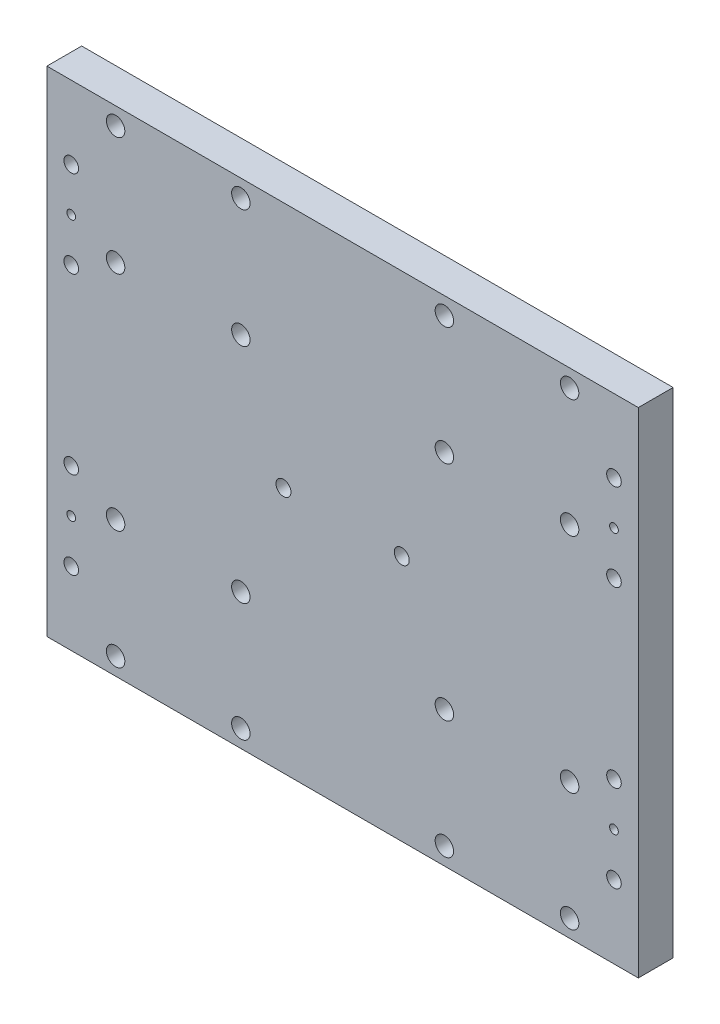
SolidWorks part; units mm, degrees
ref_plane "Front Plane" through (0, 0, 0) normal (0, 0, 1) x (1, 0, 0)
ref_plane "Top Plane" through (0, 0, 0) normal (0, 1, 0) x (1, 0, 0)
ref_plane "Right Plane" through (0, 0, 0) normal (1, 0, 0) x (0, 0, -1)
sketch "Sketch1" plane through (0, 0, 0) normal (0, 0, 1) x (1, 0, 0)
  line L1 (85, -71) -> (-85, -71)
  line L2 (85, -71) -> (85, 71)
  line L3 (85, 71) -> (-85, 71)
  line L4 (-85, -71) -> (-85, 71)
  line L5 (85, -71) -> (-85, 71) construction
  line L6 (85, 71) -> (-85, -71) construction
  point P0 (0, 0)
  dimension "D1" = 170
  dimension "D2" = 142
extrude "Boss-Extrude1" add sketch "Sketch1" along normal mid plane 10
hole_wizard "M5 Clearance Hole1" positions "Sketch8" profile "Sketch7" hole size "M5" standard "ANSI Metric" end condition through all
sketch "Sketch8" plane through (0, 0, 5) normal (0, 0, 1) x (1, 0, 0)
  line L1 (-29.25, 32) -> (-65.25, 32) construction
  line L2 (-29.25, 32) -> (-29.25, 66) construction
  line L3 (-29.25, 66) -> (-65.25, 66) construction
  line L4 (-65.25, 32) -> (-65.25, 66) construction
  line L5 (-29.25, 32) -> (-65.25, 66) construction
  line L6 (-29.25, 66) -> (-65.25, 32) construction
  line L9 (85, 71) -> (-85, 71) construction
  line L10 (-85, 71) -> (-85, -71) construction
  point P0 (-65.25, 66)
  point P2 (-29.25, 66)
  point P4 (-29.25, 32)
  point P6 (-65.25, 32)
  dimension "D1" = 5
  dimension "D2" = 19.75
  dimension "D3" = 34
  dimension "D4" = 36
sketch "Sketch7" plane through (-65.25, 66, 5) normal (1, 0, 0) x (0, -1, 0)
  line L0 (0, 0) -> (0, 10)
  line L1 (0, 10) -> (2.65, 10)
  line L2 (2.65, 10) -> (2.65, 0)
  line L5 (2.65, 0) -> (0, 0)
  line L11 (0, -6.35) -> (0, 107.95) construction
  dimension "Thru Hole Dia." = 5.3
  dimension "Thru Hole Depth" = 10
mirror "Mirror2" about plane through (0, 0, 0) normal (0, 1, 0) of "M5 Clearance Hole1"
mirror "Mirror3" about plane through (0, 0, 0) normal (1, 0, 0) of "Mirror2"
hole_wizard "M4 Clearance Hole1" positions "Sketch10" profile "Sketch9" hole size "M4" standard "ANSI Metric" end condition through all
sketch "Sketch10" plane through (0, 0, 5) normal (0, 0, 1) x (1, 0, 0)
  line L0 (-1000, 0) -> (49000, 0) construction
  point P0 (-17, 0)
  point P2 (17, 0)
  dimension "D1" = 17
  dimension "D2" = 17
sketch "Sketch9" plane through (-17, 0, 5) normal (1, 0, 0) x (0, -1, 0)
  line L0 (0, 0) -> (0, 10)
  line L1 (0, 10) -> (2.15, 10)
  line L2 (2.15, 10) -> (2.15, 0)
  line L5 (2.15, 0) -> (0, 0)
  line L11 (0, -6.35) -> (0, 107.95) construction
  dimension "Thru Hole Dia." = 4.3
  dimension "Thru Hole Depth" = 10
hole_wizard "M5x0.8 Tapped Hole1" positions "Sketch12" profile "Sketch11" tap size "M5x0.8" standard "ANSI Metric"
sketch "Sketch12" plane through (0, 0, 5) normal (0, 0, 1) x (1, 0, 0)
  line L0 (-78, -1023.3996) -> (-78, 48976.6004) construction
  line L1 (-85, 71) -> (-85, -71) construction
  line L2 (-1000, 0) -> (49000, 0) construction
  point P0 (-78, 50)
  point P2 (-78, 25)
  dimension "D1" = 7
  dimension "D2" = 25
  dimension "D3" = 50
sketch "Sketch11" plane through (-78, 50, 5) normal (1, 0, 0) x (0, -1, 0)
  line L0 (0, 0) -> (0, 15.2618)
  line L1 (0, 15.2618) -> (2.1, 14)
  line L2 (2.1, 14) -> (2.1, 0)
  line L5 (2.1, 0) -> (0, 0)
  line L10 (0, 15.2618) -> (-2.1, 14) construction
  line L11 (0, -6.35) -> (0, 107.95) construction
  dimension "Tap Drill Dia." = 4.2
  dimension "Tap Drill Depth" = 14
  dimension "Drill Angle" = 118
cosmetic thread "Hole Thread1" parameters "D1"=10, "D2"=5
cosmetic thread "Hole Thread2" parameters "D1"=10, "D2"=5
sketch "Sketch6" plane through (0, 0, 5) normal (0, 0, 1) x (1, 0, 0)
  line L0 (-78, -1002.1032) -> (-78, 48997.8968) construction
  line L1 (78, -1010.3548) -> (78, 48989.6452) construction
  line L2 (-85, 71) -> (-85, -71) construction
  line L3 (85, -71) -> (85, 71) construction
  line L6 (-1000, 0) -> (49000, 0) construction
  circle A1 centre (-78, 37.5) radius 1.25
  dimension "D4" = 2.5
  dimension "D1" = 7
  dimension "D2" = 7
  dimension "D10" = 37.5
extrude "Cut-Extrude5" cut sketch "Sketch6" against normal through all
mirror "Mirror1" about plane through (0, 0, 0) normal (1, 0, 0) of "M5x0.8 Tapped Hole1", "Cut-Extrude5"
mirror "Mirror4" about plane through (0, 0, 0) normal (0, 1, 0) of "Mirror1"
